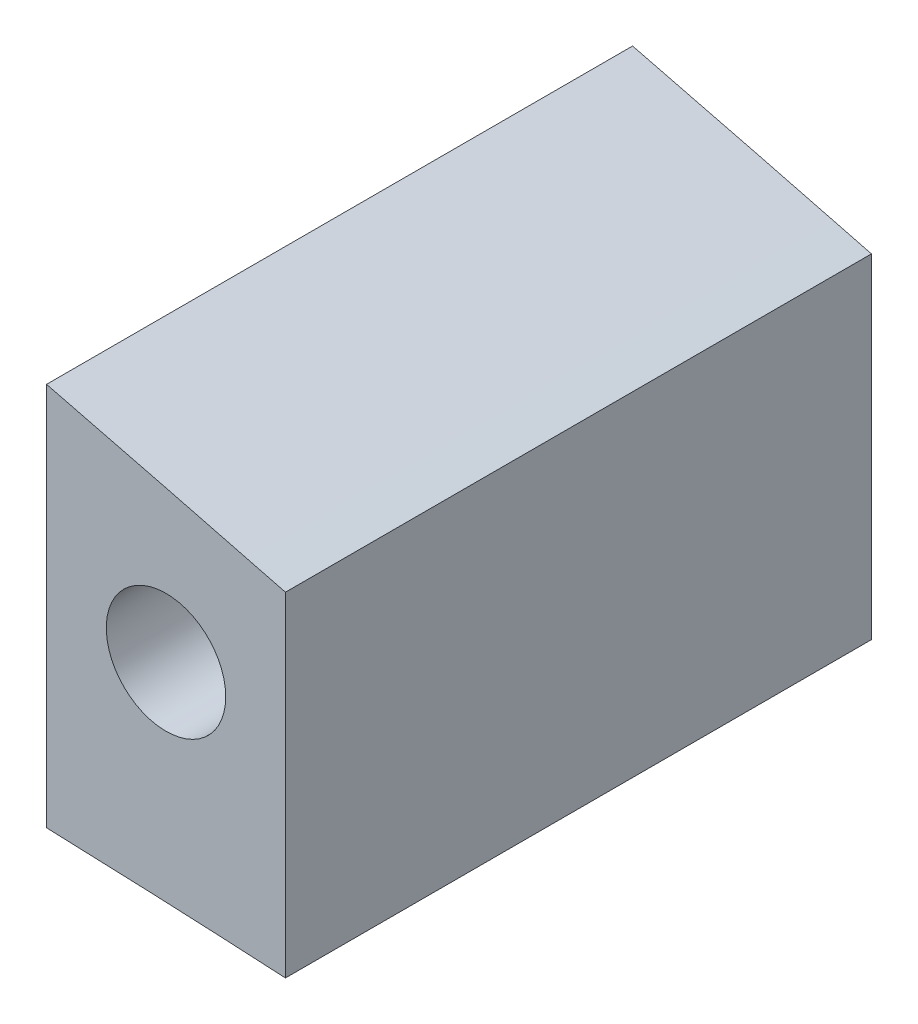
SolidWorks part; units mm, degrees
ref_plane "Front Plane" through (0, 0, 0) normal (0, 0, 1) x (1, 0, 0)
ref_plane "Top Plane" through (0, 0, 0) normal (0, 1, 0) x (1, 0, 0)
ref_plane "Right Plane" through (0, 0, 0) normal (1, 0, 0) x (0, 0, -1)
sketch "Sketch1" plane through (0, 0, 0) normal (0, 0, 1) x (1, 0, 0)
  spline S0 degree 3 poles (0.0006, 0.0001) (0.8106, 7.3592) (8.6491, 17.8566) (26.2867, 29.9752) (52.1111, 42.0692) (89.5976, 49.2908) (131.4008, 47.8848) (173.2567, 40.0411) (217.9611, 29.613) (256.9521, 19.5289) (290.3598, 8.711) (301.2732, 4.3828) (314.8169, -0.5162) (309.8463, 0.0001) knots 0 0 0 0 0.060864 0.113688 0.188609 0.312909 0.448482 0.557612 0.691544 0.852438 0.929756 0.976058 1 1 1 1
  spline S1 degree 3 poles (309.8463, 0.0001) (303.9568, 1.471) (293.9895, 2.094) (276.264, 4.5144) (260.8463, 5.4274) (235.8588, 7.8703) (205.1014, 8.8381) (157.7186, 9.0307) (110.4973, 6.1815) (66.5062, -0.5867) (36.4547, -6.0985) (15.3166, -6.1891) (1.2307, -6.9241) (0.0006, 0.0001) knots 0 0 0 0 0.057787 0.095275 0.171021 0.205339 0.335319 0.464904 0.658702 0.785512 0.893517 0.943092 1 1 1 1
extrude "Boss-Extrude1" add sketch "Sketch1" along normal blind 31.1531
sketch "Sketch2" plane through (0, 0, 31.1531) normal (0, 0, 1) x (1, 0, 0)
  circle A0 centre (20.32, 10.16) radius 6.35
  circle A1 centre (227.2963, 19.0501) radius 3.175
  dimension "D2" = 12.7
  dimension "D3" = 6.35
  dimension "D6" = 20.32
  dimension "D1" = 82.55
  dimension "D4" = 19.05
  dimension "D5" = 10.16
extrude "Cut-Extrude1" cut sketch "Sketch2" against normal through all
sketch "Sketch3" plane through (0, 0, 31.1531) normal (0, 0, 1) x (1, 0, 0)
  line L1 (350.4863, -6.3499) -> (233.6463, -6.3499)
  line L2 (350.4863, -6.3499) -> (350.4863, 44.4501)
  line L3 (350.4863, 44.4501) -> (233.6463, 44.4501)
  line L4 (233.6463, -6.3499) -> (233.6463, 44.4501)
  circle A0 centre (227.2963, 19.0501) radius 3.175 construction
  dimension "D1" = 6.35
  dimension "D2" = 116.84
  dimension "D3" = 50.8
  dimension "D4" = 44.45
extrude "Cut-Extrude2" cut sketch "Sketch3" against normal through all contours L3 L4 L1 L2
sketch "Sketch4" plane through (0, 0, 31.1531) normal (0, 0, 1) x (1, 0, 0)
  line L0 (233.6463, 7.6905) -> (233.6463, 25.4528) construction
  line L1 (220.9463, -24.2166) -> (-29.2042, -24.2166)
  line L2 (220.9463, -24.2166) -> (220.9463, 93.2727)
  line L3 (220.9463, 93.2727) -> (-29.2042, 93.2727)
  line L4 (-29.2042, -24.2166) -> (-29.2042, 93.2727)
  dimension "D1" = 12.7
extrude "Cut-Extrude3" cut sketch "Sketch4" against normal through all
